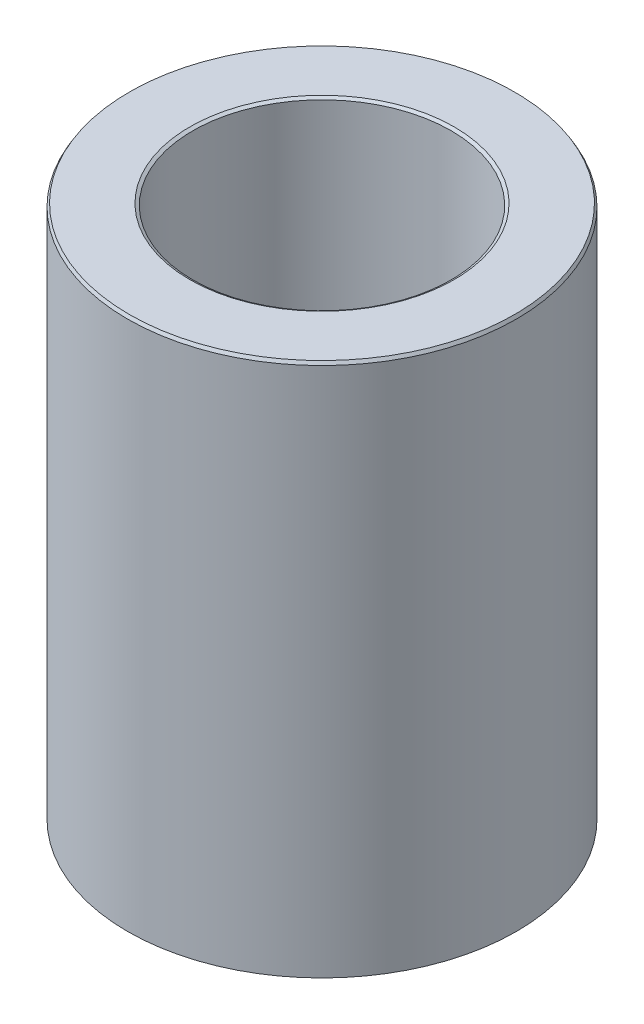
SolidWorks part; units mm, degrees
ref_plane "Front Plane" through (0, 0, 0) normal (0, 0, 1) x (1, 0, 0)
ref_plane "Top Plane" through (0, 0, 0) normal (0, 1, 0) x (1, 0, 0)
ref_plane "Right Plane" through (0, 0, 0) normal (1, 0, 0) x (0, 0, -1)
sketch "Sketch1" plane through (0, 0, 0) normal (0, 1, 0) x (1, 0, 0)
  circle A0 centre (0, 0) radius 57.5
  dimension "SLEEVE_OD" = 115
extrude "Boss-Extrude1" add sketch "Sketch1" along normal blind 158.2633
sketch "Sketch2" plane through (0, 0, 0) normal (0, 1, 0) x (1, 0, 0)
  circle A0 centre (0, 0) radius 38.2069
  dimension "BORE_D" = 76.4138
extrude "Cut-Extrude1" cut sketch "Sketch2" along normal through all
chamfer "Chamfer1" distance 0.9077 angle 30 4 edges at (0, 158.2633, 38.2069) (0, 0, 38.2069) (0, 0, 57.5) (0, 158.2633, 57.5) first distance on face at (0, 158.2633, 38.2069) first distance on face at (0, 0, 38.2069) first distance on face at (0, 158.2633, 57.5)
